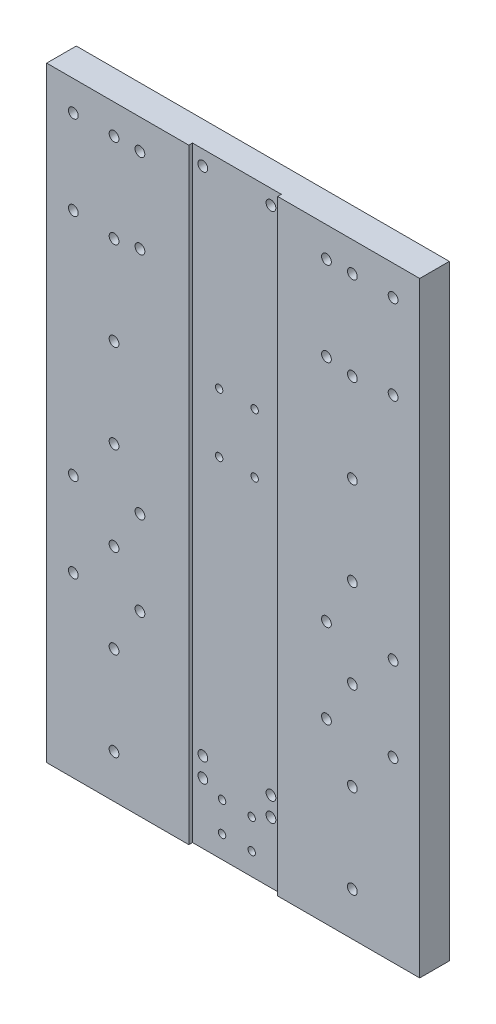
SolidWorks part; units mm, degrees
ref_plane "Piano frontale" through (0, 0, 0) normal (0, 0, 1) x (1, 0, 0)
ref_plane "Piano superiore" through (0, 0, 0) normal (0, 1, 0) x (1, 0, 0)
ref_plane "Piano destro" through (0, 0, 0) normal (1, 0, 0) x (0, 0, -1)
sketch "Schizzo1" plane through (0, 0, 0) normal (0, 0, 1) x (1, 0, 0)
  line L1 (126, -250) -> (-126, -250)
  line L2 (126, -250) -> (126, 250)
  line L3 (126, 250) -> (-126, 250)
  line L4 (-126, -250) -> (-126, 250)
  line L5 (126, -250) -> (-126, 250) construction
  line L6 (126, 250) -> (-126, -250) construction
  point P0 (0, 0)
  dimension "D1" = 252
  dimension "D2" = 500
extrude "Estrusione-Estrusione1" add sketch "Schizzo1" along normal blind 20
sketch "Schizzo2" plane through (0, 0, 20) normal (0, 0, 1) x (1, 0, 0)
  line L0 (1265.2426, 21.4119) -> (-695.7574, 21.4119) construction
  line L1 (1265.2426, 13.5541) -> (-695.7574, 13.5541) construction
  line L2 (1265.2426, 53.5541) -> (-695.7574, 53.5541) construction
  line L3 (1265.2426, 61.4119) -> (-695.7574, 61.4119) construction
  line L4 (-126, 250) -> (-126, -250)
  line L5 (-126, -250) -> (126, -250)
  line L6 (126, -250) -> (126, 250)
  line L7 (126, 250) -> (-126, 250)
  line L8 (-126, 250) -> (-126, -250) construction
  line L9 (-126, -250) -> (126, -250) construction
  line L10 (126, -250) -> (126, 250) construction
  line L11 (126, 250) -> (-126, 250) construction
  line L12 (1265.2426, 21.4119) -> (-695.7574, 21.4119) construction
  line L13 (1265.2426, 13.5541) -> (-695.7574, 13.5541) construction
  line L14 (1265.2426, 53.5541) -> (-695.7574, 53.5541) construction
  line L15 (1265.2426, 61.4119) -> (-695.7574, 61.4119) construction
  line L16 (126, -45.017) -> (-126, -45.017) construction
  line L17 (126, -25.017) -> (-126, -25.017) construction
  line L18 (126, -45.017) -> (-126, -45.017) construction
  line L19 (126, -25.017) -> (-126, -25.017) construction
  line L20 (-126, -45.017) -> (-126, -25.017) construction
  line L21 (126, -35.017) -> (-126, -35.017) construction
  line L22 (-126, -45.017) -> (126, -45.017) construction
  line L23 (-126, -45.017) -> (-126, -25.017) construction
  line L24 (-126, -25.017) -> (126, -25.017) construction
  line L25 (126, -45.017) -> (126, -25.017) construction
  circle A0 centre (110, 17.483) radius 3.9289
  circle A1 centre (110, 57.483) radius 3.9289
  circle A2 centre (-110, 17.483) radius 3.9289
  circle A3 centre (-110, 57.483) radius 3.9289
  circle A4 centre (110, -35.017) radius 3.5
  circle A5 centre (-110, -35.017) radius 3.5
  circle A6 centre (55, -35.017) radius 3.5
  circle A8 centre (-55, -35.017) radius 3.5
  circle A9 centre (20, -35.017) radius 3.5
  circle A10 centre (-20, -35.017) radius 3.5
  circle A11 centre (165, -35.017) radius 3.5 [skipped]
  dimension "D2" = 16
  dimension "D3" = 7.8579
  dimension "D4" = 16
  dimension "D5" = 7.8579
  dimension "D6" = 7
  dimension "D7" = 7
  dimension "D8" = 2
  dimension "D1" = 0
  dimension "D9" = 2
  dimension "D10" = 2
  dimension "D11" = 2
sketch "Schizzo3" plane through (0, 250, 0) normal (0, 1, 0) x (1, 0, 0)
  line L0 (126, -20) -> (-126, -20) construction
  line L1 (30, -17.5) -> (-30, -17.5)
  line L2 (30, -17.5) -> (30, -20)
  line L3 (30, -20) -> (-30, -20)
  line L4 (-30, -17.5) -> (-30, -20)
  line L5 (126, -20) -> (126, 0) construction
  line L6 (-126, -20) -> (-126, 0) construction
  line L7 (126, -20) -> (-126, -20) construction
  dimension "D1" = 2.5
  dimension "D2" = 96
  dimension "D3" = 96
extrude "Taglio-Estrusione1" cut sketch "Schizzo3" against normal through all
sketch "Schizzo4" plane through (0, 0, 17.5) normal (0, 0, 1) x (1, 0, 0)
  line L0 (30, -250) -> (30, 250) construction
  line L2 (30, 250) -> (-30, 250) construction
  line L3 (30, -250) -> (30, 250) construction
  line L6 (-30, 250) -> (-126, 250) construction
  line L7 (-30, -250) -> (-30, 250) construction
  point P11 (23, -118)
  point P14 (-23, -118)
  point P15 (-23, -105)
  point P16 (23, -105)
  point P17 (23, 240)
  point P18 (-23, 240)
  dimension "D1" = 46
  dimension "D2" = 13
  dimension "D3" = 13
  dimension "D4" = 46
  dimension "D5" = 7
  dimension "D6" = 345
  dimension "D7" = 10
  dimension "D8" = 46
  dimension "D9" = 7
  dimension "D10" = 10
  dimension "D11" = 7
  dimension "D12" = 7
sketch "Schizzo5" plane through (0, 0, 20) normal (0, 0, 1) x (1, 0, 0)
  point P4 (80.5006, 170)
  point P7 (80.5006, 110)
  point P16 (80.5006, 50)
  point P17 (80.5006, -10)
  point P18 (80.5006, -70)
  point P19 (80.5006, -130)
  point P20 (80.5006, 230)
hole_wizard "M6 Clearance Hole2" positions "Sketch7" profile "Sketch8" hole size "M6" standard "ISO"
sketch "Sketch7" plane through (0, 0, 20) normal (0, 0, 1) x (1, 0, 0)
  point P0 (80.5006, -130)
  point P3 (80.5006, -70)
  point P7 (80.5006, -10)
  point P10 (80.5006, 50)
  point P13 (80.5006, 110)
  point P16 (80.5006, 170)
  point P19 (80.5006, 230)
sketch "Sketch8" plane through (80.5006, -130, 20) normal (1, 0, 0) x (0, -1, 0)
  line L0 (0, 0) -> (0, 38.5828)
  line L1 (0, 38.5828) -> (3.3, 36.6)
  line L2 (3.3, 36.6) -> (3.3, 0)
  line L5 (3.3, 0) -> (0, 0)
  line L10 (0, 38.5828) -> (-3.3, 36.6) construction
  line L11 (0, -6.35) -> (0, 107.95) construction
  dimension "Hole Dia." = 6.6
  dimension "Hole Depth" = 36.6
  dimension "Drill Angle" = 118
sketch "Schizzo6" plane through (0, 0, 20) normal (0, 0, 1) x (1, 0, 0)
  line L0 (126, -250) -> (126, 250) construction
  line L2 (126, 250) -> (30, 250) construction
  point P23 (108, 172.8083)
  point P26 (63, 172.8083)
  point P27 (63, 229.8083)
  point P28 (108, 229.8083)
  dimension "D1" = 45
  dimension "D2" = 45
  dimension "D3" = 57
  dimension "D4" = 57
  dimension "D5" = 18
  dimension "D6" = 20.1917
  dimension "D7" = 20.1917
  dimension "D8" = 18
hole_wizard "M6 Clearance Hole4" positions "Sketch14" profile "Sketch15" hole size "M6" standard "ISO"
sketch "Sketch14" plane through (0, 0, 20) normal (0, 0, 1) x (1, 0, 0)
  point P0 (108, 172.8083)
  point P3 (108, 229.8083)
  point P6 (63, 229.8083)
  point P9 (63, 172.8083)
  point P12 (63, 17.8083)
  point P14 (63, -39.1917)
  point P16 (108, -39.1917)
  point P18 (108, 17.8083)
sketch "Sketch15" plane through (108, 172.8083, 20) normal (1, 0, 0) x (0, -1, 0)
  line L0 (0, 0) -> (0, 38.5828)
  line L1 (0, 38.5828) -> (3.3, 36.6)
  line L2 (3.3, 36.6) -> (3.3, 0)
  line L5 (3.3, 0) -> (0, 0)
  line L10 (0, 38.5828) -> (-3.3, 36.6) construction
  line L11 (0, -6.35) -> (0, 107.95) construction
  dimension "Hole Dia." = 6.6
  dimension "Hole Depth" = 36.6
  dimension "Drill Angle" = 118
hole_wizard "M6 Clearance Hole3" positions "Sketch9" profile "Sketch10" hole size "M6" standard "ISO"
sketch "Sketch9" plane through (0, 0, 17.5) normal (0, 0, 1) x (1, 0, 0)
  point P0 (23, -118)
  point P3 (23, -105)
  point P6 (-23, -118)
  point P9 (-23, -105)
  point P12 (23, 240)
  point P15 (-23, 240)
sketch "Sketch10" plane through (23, -118, 17.5) normal (1, 0, 0) x (0, -1, 0)
  line L0 (0, 0) -> (0, 38.5828)
  line L1 (0, 38.5828) -> (3.3, 36.6)
  line L2 (3.3, 36.6) -> (3.3, 0)
  line L5 (3.3, 0) -> (0, 0)
  line L10 (0, 38.5828) -> (-3.3, 36.6) construction
  line L11 (0, -6.35) -> (0, 107.95) construction
  dimension "Hole Dia." = 6.6
  dimension "Hole Depth" = 36.6
  dimension "Drill Angle" = 118
sketch "Sketch11" plane through (0, 0, 17.5) normal (0, 0, 1) x (1, 0, 0)
  line L0 (0, -250) -> (0, 250) construction
  line L1 (30, -250) -> (-30, -250) construction
  line L2 (30, 250) -> (-30, 250) construction
ref_plane "Plane1" through (0, 0, 0) normal (-1, 0, 0) x (0, 0, 1)
mirror "Mirror1" about plane through (0, 0, 0) normal (-1, 0, 0) of "M6 Clearance Hole2"
mirror "Mirror2" about plane through (0, 0, 0) normal (-1, 0, 0) of "M6 Clearance Hole4"
sketch "Sketch16" plane through (0, 0, 0) normal (0, 0, -1) x (-1, 0, 0)
  line L0 (126, 250) -> (126, -250) construction
  line L1 (126, -317.9299) -> (-126, -317.9299)
  line L2 (126, -317.9299) -> (126, -159.25)
  line L3 (126, -159.25) -> (-126, -159.25)
  line L4 (-126, -317.9299) -> (-126, -159.25)
  line L5 (-126, -250) -> (-126, 250) construction
  line L9 (-12.9, -159.25) -> (25.2, -159.25) construction
extrude "Cut-Extrude1" cut sketch "Sketch16" against normal blind 28
hole_wizard "Tap Drill for M6 Tap1" positions "Sketch17" profile "Sketch18" hole size "M6" standard "ISO" end condition through all
sketch "Sketch17" plane through (0, 0, 17.5) normal (0, 0, 1) x (1, 0, 0)
  line L0 (12, 75.3083) -> (-12, 115.3083) construction
  line L1 (-12, 115.3083) -> (-12, 75.3083) construction
  line L2 (-12, 75.3083) -> (12, 115.3083) construction
  line L3 (12, 115.3083) -> (12, 75.3083) construction
  line L4 (12, 75.3083) -> (-12, 75.3083) construction
  line L7 (-12, 115.3083) -> (12, 115.3083) construction
  point P0 (-12, 75.3083)
  point P2 (12, 75.3083)
  point P4 (12, 115.3083)
  point P6 (-12, 115.3083)
  dimension "D1" = 40
  dimension "D2" = 24
sketch "Sketch18" plane through (-12, 75.3083, 17.5) normal (1, 0, 0) x (0, -1, 0)
  line L0 (0, 0) -> (0, 17.5)
  line L1 (0, 17.5) -> (2.5, 17.5)
  line L2 (2.5, 17.5) -> (2.5, 0)
  line L5 (2.5, 0) -> (0, 0)
  line L11 (0, -6.35) -> (0, 107.95) construction
  dimension "Thru Hole Dia." = 5
  dimension "Thru Hole Depth" = 17.5
sketch "Sketch19" plane through (0, -195.45, 0) normal (0, -1, 0) x (-1, 0, 0)
  line L0 (0, -70.7) -> (0, 68.239) construction
  line L1 (126, -10) -> (-126, -10) construction
  line L2 (126, -20) -> (126, 0) construction
  line L3 (-126, -20) -> (-126, 0) construction
  line L5 (28.2, 0) -> (-28.2, 0) construction
  point P8 (20, -10)
  point P9 (-20, -10)
  point P12 (-20, 10)
  point P13 (20, 10)
  dimension "D1" = 20
hole_wizard "Tap Drill for M6 Tap2" positions "Sketch22" profile "Sketch23" hole size "M6" standard "ISO"
sketch "Sketch22" plane through (0, -159.25, 0) normal (0, -1, 0) x (-1, 0, 0)
  point P0 (20, -10)
  point P2 (-20, -10)
sketch "Sketch23" plane through (-20, -159.25, 10) normal (1, 0, 0) x (0, 0, -1)
  line L0 (0, 0) -> (0, 31.5022)
  line L1 (0, 31.5022) -> (2.5, 30)
  line L2 (2.5, 30) -> (2.5, 0)
  line L5 (2.5, 0) -> (0, 0)
  line L10 (0, 31.5022) -> (-2.5, 30) construction
  line L11 (0, -6.35) -> (0, 107.95) construction
  dimension "Hole Dia." = 5
  dimension "Hole Depth" = 30
  dimension "Drill Angle" = 118
hole_wizard "Tap Drill for M6 Tap3" positions "Sketch24" profile "Sketch25" hole size "M6" standard "ISO" end condition through all
sketch "Sketch24" plane through (0, 0, 0) normal (0, 0, -1) x (-1, 0, 0)
  point P0 (-10, -144.25)
  point P2 (-10, -124.25)
  point P4 (10, -124.25)
  point P6 (10, -144.25)
sketch "Sketch25" plane through (10, -144.25, 0) normal (1, 0, 0) x (0, 1, 0)
  line L0 (0, 0) -> (0, 20)
  line L1 (0, 20) -> (2.5, 20)
  line L2 (2.5, 20) -> (2.5, 0)
  line L5 (2.5, 0) -> (0, 0)
  line L11 (0, -6.35) -> (0, 107.95) construction
  dimension "Thru Hole Dia." = 5
  dimension "Thru Hole Depth" = 20
equation "\"D3@Schizzo3\"=\"D2@Schizzo3\""
equation "\"D11@Schizzo4\"=\"D5@Schizzo4\""
